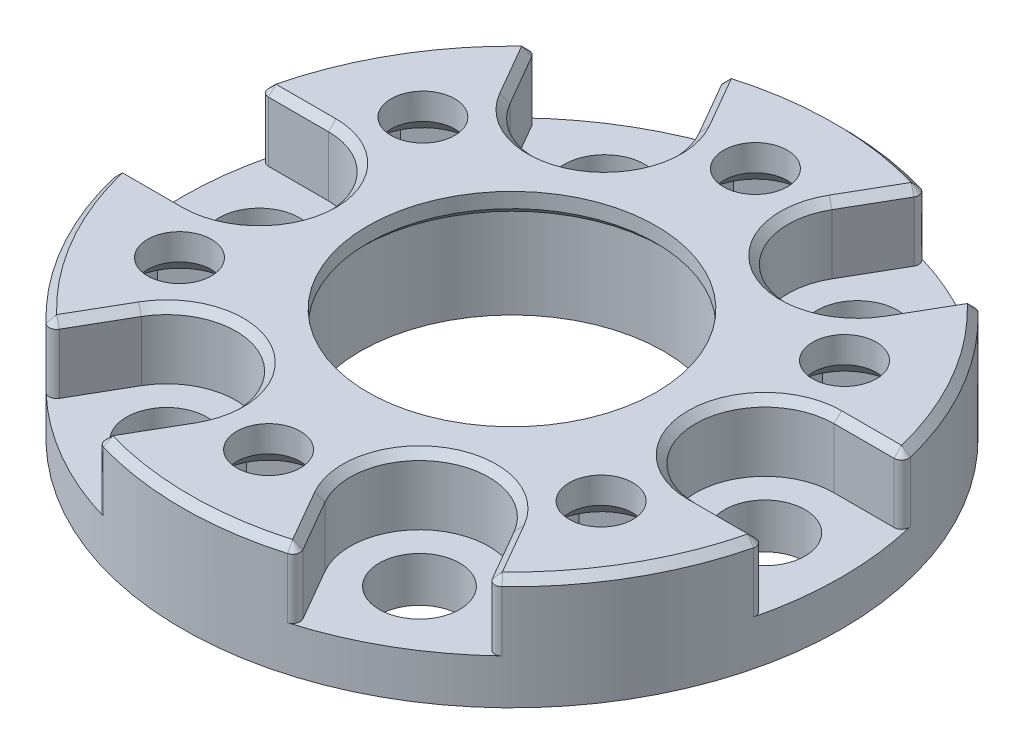
SolidWorks part; units mm, degrees
material "ABS"
ref_plane "Front Plane" through (0, 0, 0) normal (0, 0, 1) x (1, 0, 0)
ref_plane "Top Plane" through (0, 0, 0) normal (0, 1, 0) x (1, 0, 0)
ref_plane "Right Plane" through (0, 0, 0) normal (1, 0, 0) x (0, 0, -1)
sketch "Sketch1" plane through (0, 0, 0) normal (0, 1, 0) x (1, 0, 0)
  circle A0 centre (0, 0) radius 17.5
  circle A1 centre (0, 0) radius 8
  dimension "D1" = 35
  dimension "D2" = 16
sketch "Sketch8" plane through (0, 0, 0) normal (0, 0, 1) x (1, 0, 0)
  line L0 (8.1, 0) -> (8.1, 4.8)
  line L2 (7.7, 6) -> (17.6, 6)
  line L3 (17.6, 6) -> (17.6, 0)
  line L4 (17.6, 0) -> (8.1, 0)
  line L5 (0, 16.9727) -> (0, -11.1077) construction
  line L6 (7.7, 6) -> (7.7, 5.2)
  line L7 (7.7, 5.2) -> (8.1, 4.8)
  dimension "D1" = 8.1
  dimension "D2" = 17.6
  dimension "D3" = 6
  dimension "D4" = 0.4
  dimension "D5" = 1.2
  dimension "D6" = 45
revolve "Revolve1" add sketch "Sketch8" angle 360 about L5
sketch "Sketch2" plane through (0, 6, 0) normal (0, 1, 0) x (1, 0, 0)
  line L0 (13.5, 3.7) -> (17.2067, 3.7)
  line L1 (13.5, -3.7) -> (17.2067, -3.7)
  line L2 (0, 0) -> (13.5, 0) construction
  arc A0 (13.5, 3.7) -> (13.5, -3.7) centre (13.5, 0) ccw
  arc A2 (17.2067, 3.7) -> (17.2067, -3.7) centre (0, 0) cw
  circle A3 centre (0, 0) radius 17.6 construction
  dimension "D1" = 3.7
  dimension "D2" = 13.5
extrude "Cut-Extrude1" cut sketch "Sketch2" against normal offset from surface (3.6 mm away) 2.4 up to face at (-17.6, 0, 0)
sketch "Sketch5" plane through (0, 0, 0) normal (0, -1, 0) x (1, 0, 0)
  line L0 (0, 0) -> (0, -13) construction
  line L1 (2.8, -14.6166) -> (2.8, -11.3834)
  line L2 (2.8, -11.3834) -> (0, -9.7668)
  line L3 (0, -9.7668) -> (-2.8, -11.3834)
  line L4 (-2.8, -11.3834) -> (-2.8, -14.6166)
  line L5 (-2.8, -14.6166) -> (0, -16.2332)
  line L6 (0, -16.2332) -> (2.8, -14.6166)
  circle A0 centre (0, -13) radius 2.8 construction
  dimension "D1" = 13
  dimension "D2" = 5.6
extrude "Cut-Extrude2" cut sketch "Sketch5" against normal blind 3.6
hole_wizard "M3 Clearance Hole3" positions "Sketch6" profile "Sketch7" hole size "M3" standard "ISO" end condition through all
sketch "Sketch6" plane through (0, 6, 0) normal (0, 1, 0) x (1, 0, 0)
  point P0 (0, 13)
sketch "Sketch7" plane through (0, 6, -13) normal (1, 0, 0) x (0, 0, 1)
  line L0 (0, 0) -> (0, 6)
  line L1 (0, 6) -> (1.7, 6)
  line L2 (1.7, 6) -> (1.7, 0)
  line L5 (1.7, 0) -> (0, 0)
  line L11 (0, -6.35) -> (0, 107.95) construction
  dimension "Thru Hole Dia." = 3.4
  dimension "Thru Hole Depth" = 6
chamfer "Chamfer2" distance 1 angle 45 1 edges at (1.7, 3.6, -13)
hole_wizard "M4 Clearance Hole2" positions "Sketch9" profile "Sketch10" hole size "M4" standard "ISO" end condition through all
sketch "Sketch9" plane through (0, 2.4, 0) normal (0, 1, 0) x (1, 0, 0)
  point P0 (13.5, 0)
sketch "Sketch10" plane through (13.5, 2.4, 0) normal (1, 0, 0) x (0, 0, 1)
  line L0 (0, 0) -> (0, 2.4)
  line L1 (0, 2.4) -> (2.15, 2.4)
  line L2 (2.15, 2.4) -> (2.15, 0)
  line L5 (2.15, 0) -> (0, 0)
  line L11 (0, -6.35) -> (0, 107.95) construction
  dimension "Thru Hole Dia." = 4.3
  dimension "Thru Hole Depth" = 2.4
pattern_circular "CirPattern2" count 6 over 360 about axis through (0, 16.9727, 0) along (0, 1, 0) of "Cut-Extrude1", "Cut-Extrude2", "M3 Clearance Hole3", "M4 Clearance Hole2", "Chamfer2" reverse direction yes
fillet "Fillet1" radius 0.4 12 edges at (-5.399, 4.2, 16.7514) (-11.8076, 4.2, 13.0514) (-17.2067, 4.2, 3.7) (-17.2067, 4.2, -3.7) (-11.8076, 4.2, -13.0514) (-5.399, 4.2, -16.7514) (5.399, 4.2, -16.7514) (11.8076, 4.2, -13.0514) (17.2067, 4.2, -3.7) (17.2067, 4.2, 3.7) (11.8076, 4.2, 13.0514) (5.399, 4.2, 16.7514)
chamfer "Chamfer1" distance 0.4 angle 45 36 edges at (4.9, 6, -8.487) (10.7553, 6, -11.2288) (4.3468, 6, -14.9288) (11.8464, 6, -12.8123) (5.1725, 6, -16.6654) (15.242, 6, -8.8) (0, 6, -17.6) (17.0189, 6, -3.8532) (-5.1725, 6, -16.6654) (15.1021, 6, -3.7) (-4.3468, 6, -14.9288) (9.8, 6, 0) (-4.9, 6, -8.487) (15.1021, 6, 3.7) (-10.7553, 6, -11.2288) (17.0189, 6, 3.8532) (-11.8464, 6, -12.8123) (15.242, 6, 8.8) (-15.242, 6, -8.8) (11.8464, 6, 12.8123) (-17.0189, 6, -3.8532) (10.7553, 6, 11.2288) (-15.1021, 6, -3.7) (4.9, 6, 8.487) (-9.8, 6, 0) (4.3468, 6, 14.9288) (-15.1021, 6, 3.7) (5.1725, 6, 16.6654) (-17.0189, 6, 3.8532) (0, 6, 17.6) (-15.242, 6, 8.8) (-5.1725, 6, 16.6654) (-11.8464, 6, 12.8123) (-4.3468, 6, 14.9288) (-10.7553, 6, 11.2288) (-4.9, 6, 8.487)
